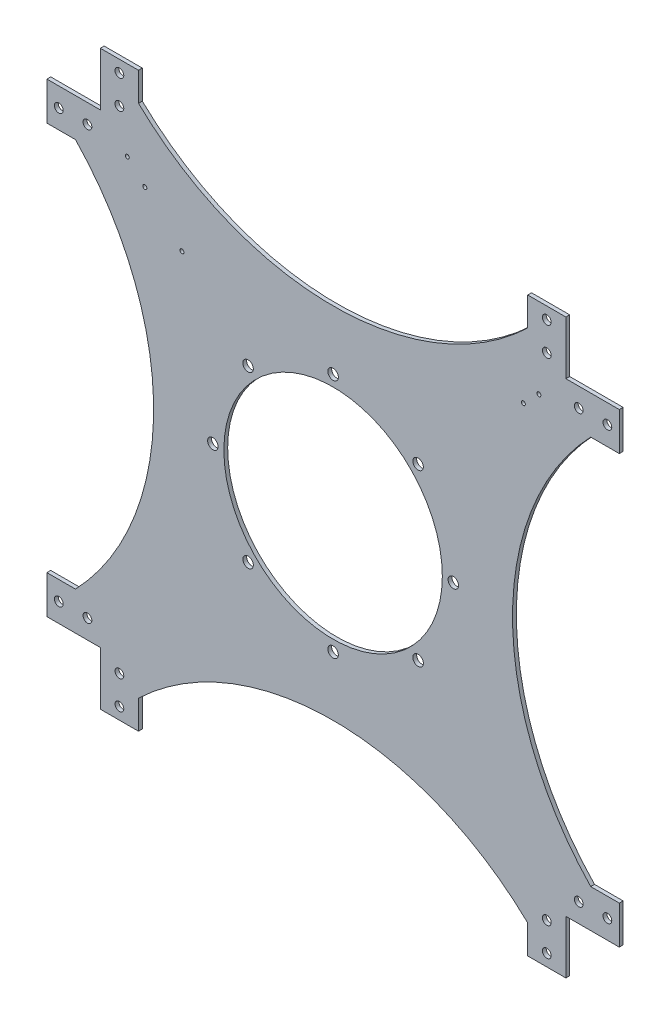
SolidWorks part; units mm, degrees
ref_plane "Front Plane" through (0, 0, 0) normal (0, 0, 1) x (1, 0, 0)
ref_plane "Top Plane" through (0, 0, 0) normal (0, 1, 0) x (1, 0, 0)
ref_plane "Right Plane" through (0, 0, 0) normal (1, 0, 0) x (0, 0, -1)
sketch "Sketch1" plane through (0, 0, 0) normal (0, 0, 1) x (1, 0, 0)
  line L0 (0, 0) -> (367.2182, 0) construction
  line L1 (0, 0) -> (0, -316.5866) construction
  line L2 (0, 0) -> (244, 244) construction
  line L3 (0, 0) -> (244, -244) construction
  line L4 (244, 244) -> (244, 300)
  line L5 (244, 244) -> (300, 244)
  line L6 (244, 300) -> (204, 300)
  line L7 (204, 300) -> (204, 270)
  line L8 (0, 0) -> (-244, 244) construction
  line L9 (0, 0) -> (-244, -244) construction
  line L10 (0, 0) -> (-199.7109, 0) construction
  line L11 (-244, 244) -> (-244, 300)
  line L12 (-244, 300) -> (-204, 300)
  line L13 (-204, 300) -> (-204, 270)
  line L14 (244, -244) -> (300, -244)
  line L15 (300, -244) -> (300, -204)
  line L16 (300, -204) -> (270, -204)
  line L17 (300, 244) -> (300, 204)
  line L18 (300, 204) -> (270, 204)
  line L19 (244, -244) -> (244, -300)
  line L20 (244, -300) -> (204, -300)
  line L21 (204, -300) -> (204, -270)
  line L22 (-204, -300) -> (-204, -270)
  line L23 (-244, -300) -> (-204, -300)
  line L24 (-244, -244) -> (-244, -300)
  line L25 (-244, -244) -> (-300, -244)
  line L26 (-300, -244) -> (-300, -204)
  line L27 (-300, -204) -> (-270, -204)
  line L28 (-300, 204) -> (-270, 204)
  line L29 (-300, 244) -> (-300, 204)
  line L30 (-244, 244) -> (-300, 244)
  circle A0 centre (0, 0) radius 114.5
  arc A1 (-204, 270) -> (204, 270) centre (0, 483.0939) ccw
  arc A2 (270, 204) -> (270, -204) centre (483.0939, 0) ccw
  arc A3 (-204, -270) -> (204, -270) centre (0, -483.0939) cw
  arc A4 (-270, 204) -> (-270, -204) centre (-483.0939, 0) cw
  dimension "D4" = 229
  dimension "D9" = 295
  dimension "D1" = 45
  dimension "D2" = 600
  dimension "D3" = 56
  dimension "D5" = 40
  dimension "D6" = 45
  dimension "D7" = 45
  dimension "D8" = 30
  dimension "D10" = 300
sheet metal parameters "Sheet-Metal1" thickness 4 parameters "D1"=1
base flange "Base-Flange1" sketch "Sketch1" thickness 4 reverse thickness direction yes parameters "D1"=1
sketch "Sketch2" plane through (0, 0, 4) normal (0, 0, 1) x (1, 0, 0)
  line L0 (244, 244) -> (244, 300) construction
  line L1 (244, 300) -> (204, 300) construction
  line L2 (300, 204) -> (300, 244) construction
  line L3 (300, 244) -> (244, 244) construction
  line L4 (0, 0) -> (260.8486, 0) construction
  line L5 (0, 0) -> (0, -250.4708) construction
  circle A0 centre (224, 287.5) radius 4.6
  circle A1 centre (224, 257.5) radius 4.6
  circle A2 centre (257.5, 224) radius 4.6
  circle A3 centre (287.5, 224) radius 4.6
  circle A4 centre (287.5, -224) radius 4.6
  circle A5 centre (257.5, -224) radius 4.6
  circle A6 centre (224, -257.5) radius 4.6
  circle A7 centre (224, -287.5) radius 4.6
  circle A8 centre (-224, -287.5) radius 4.6
  circle A9 centre (-224, -257.5) radius 4.6
  circle A10 centre (-257.5, -224) radius 4.6
  circle A11 centre (-287.5, -224) radius 4.6
  circle A12 centre (-287.5, 224) radius 4.6
  circle A13 centre (-257.5, 224) radius 4.6
  circle A14 centre (-224, 257.5) radius 4.6
  circle A15 centre (-224, 287.5) radius 4.6
  point P8 (244, 272)
  dimension "D2" = 9.2
  dimension "D1" = 20
  dimension "D3" = 12.5
  dimension "D4" = 30
  dimension "D5" = 30
  dimension "D6" = 12.5
  dimension "D7" = 20
extrude "Extrude1" cut sketch "Sketch2" against normal blind 4 normal cut yes
sketch "Sketch3" plane through (0, 0, 4) normal (0, 0, 1) x (1, 0, 0)
  line L0 (0, 0) -> (220.4396, 0) construction
  line L1 (0, 0) -> (0, -219.5819) construction
  line L2 (0, 0) -> (178.1909, 178.1909) construction
  circle A0 centre (0, 0) radius 126 construction
  circle A1 centre (0, 126) radius 5.5
  circle A2 centre (-126, 0) radius 5.5 construction
  circle A3 centre (0, -126) radius 5.5 construction
  circle A4 centre (126, 0) radius 5.5 construction
  dimension "D2" = 11
  dimension "D3" = 252
  dimension "D1" = 45
extrude "Extrude2" cut sketch "Sketch3" against normal blind 4 normal cut yes
pattern_circular "CirPattern1" count 8 over 360 about axis through (0, 0, 4) along (0, 0, 1) of "Extrude2"
sketch "Sketch4" plane through (0, 0, 4) normal (0, 0, 1) x (1, 0, 0)
  line L0 (-244, 244) -> (0, 0) construction
  line L1 (0, 0) -> (244, 244) construction
  circle A0 centre (215.7157, 215.7157) radius 2.1
  circle A1 centre (199.4523, 199.4523) radius 2.1
  circle A2 centre (-158.4401, 158.4401) radius 2.1
  circle A3 centre (-215.7157, 215.7157) radius 2.1
  circle A4 centre (-197.331, 197.331) radius 2.1
  dimension "D1" = 23
  dimension "D2" = 4.2
  dimension "D3" = 40
  dimension "D4" = 40
  dimension "D5" = 26
  dimension "D6" = 55
extrude "Cut-Extrude1" cut sketch "Sketch4" against normal blind 4 normal cut yes
flat pattern "Flat-Pattern1" [suppressed]
sketch "Bend-Lines1" plane through (0, 0, 0) normal (0, 1, 0) x (-1, 0, 0)
sketch3d "Bounding-Box1" [suppressed]
  line L0 (-783.0939, -300, 0) -> (-183.0939, -300, 0) construction
  line L1 (-783.0939, 300, 0) -> (-183.0939, 300, 0) construction
  line L2 (-783.0939, -300, 0) -> (-783.0939, 300, 0) construction
  line L3 (-183.0939, -300, 0) -> (-183.0939, 300, 0) construction
